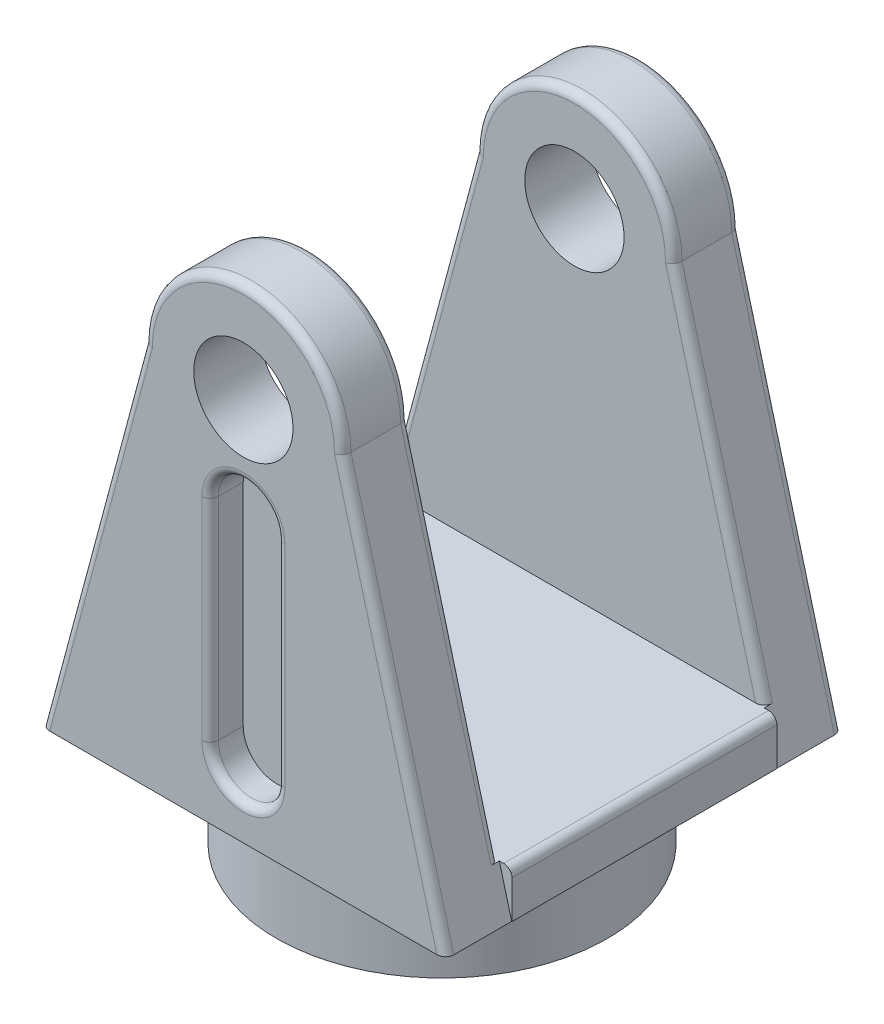
SolidWorks part; units mm, degrees
material "AISI 316 Stainless Steel Sheet (SS)"
ref_plane "Front Plane" through (0, 0, 0) normal (0, 0, 1) x (1, 0, 0)
ref_plane "Top Plane" through (0, 0, 0) normal (0, 1, 0) x (1, 0, 0)
ref_plane "Right Plane" through (0, 0, 0) normal (1, 0, 0) x (0, 0, -1)
sketch "Sketch2" plane through (0, 0, 0) normal (0, 0, 1) x (1, 0, 0)
  line L0 (-76.2, 0) -> (-155.088, -294.4142)
  line L1 (-76.2, 0) -> (-76.2, -251.8153) construction
  line L2 (76.2, 0) -> (155.088, -294.4142)
  line L3 (76.2, 0) -> (76.2, -294.4142) construction
  line L4 (-155.088, -294.4142) -> (155.088, -294.4142)
  circle A1 centre (0, 0) radius 38.1
  arc A2 (-76.2, 0) -> (76.2, 0) centre (0, 0) cw
  dimension "D1" = 310.1761
  dimension "D2" = 76.2
  dimension "D3" = 304.8
  dimension "D4" = 15
  dimension "D5" = 304.8
extrude "Boss-Extrude2" add sketch "Sketch2" along normal blind 50.8
sketch "Sketch4" plane through (0, 0, 50.8) normal (0, 0, 1) x (1, 0, 0)
  line L1 (-155.088, -294.4142) -> (155.3271, -294.4142)
  line L2 (-155.088, -294.4142) -> (-155.088, -258.9428)
  line L3 (-155.088, -258.9428) -> (155.3271, -258.9428)
  line L4 (155.3271, -294.4142) -> (155.3271, -258.9428)
extrude "Boss-Extrude4" add sketch "Sketch4" along normal blind 101.6 contours L3 L4 L1 L2
sketch "Sketch5" plane through (0, 0, 0) normal (0, 0, -1) x (-1, 0, 0)
  line L0 (0, -80.0813) -> (0, -242.2072) construction
  line L1 (25.5068, -80.0813) -> (25.5068, -242.2072)
  line L2 (-25.5068, -80.0813) -> (-25.5068, -242.2072)
  arc A0 (25.5068, -80.0813) -> (-25.5068, -80.0813) centre (0, -80.0813) ccw
  arc A1 (-25.5068, -242.2072) -> (25.5068, -242.2072) centre (0, -242.2072) ccw
  point P3 (0, -161.1443)
extrude "Cut-Extrude1" cut sketch "Sketch5" against normal blind 25.4
mirror "Mirror5" about plane through (0, 0, 152.4) normal (0, 0, -1) of bodies 109
fillet "Fillet1" radius 6.35 1 edges at (115.644, -147.2071, 304.8)
fillet "Fillet2" radius 6.35 1 edges at (-115.644, -147.2071, 304.8)
fillet "Fillet3" radius 6.35 1 edges at (0, 76.2, 304.8)
fillet "Fillet4" radius 6.35 4 edges at (0, -267.7141, 304.8) (25.5068, -161.1443, 304.8) (0, -54.5745, 304.8) (-25.5068, -161.1443, 304.8)
fillet "Fillet5" radius 6.35 15 edges at (110.8918, -129.4714, 50.8) (110.8918, -129.4714, 254) (0, -54.5745, 0) (0, -267.7141, 0) (-25.5068, -161.1443, 0) (25.5068, -161.1443, 0) (115.644, -147.2071, 0) (0, 76.2, 254) (-110.8918, -129.4714, 254) (0, 76.2, 50.8) (0, 76.2, 0) (-115.644, -147.2071, 0) (-110.8918, -129.4714, 50.8) (-155.088, -258.9428, 152.4) (155.3271, -258.9428, 152.4)
sketch "Sketch8" plane through (0, -294.4142, 0) normal (0, -1, 0) x (-1, 0, 0)
  line L0 (0, 0) -> (0, -304.8) construction
  line L1 (148.514, -304.8) -> (-148.514, -304.8) construction
  line L2 (155.088, -152.4) -> (-155.3271, -152.4) construction
  line L3 (155.088, -254) -> (155.088, -50.8) construction
  line L4 (-155.3271, -254) -> (-155.3271, -50.8) construction
  circle A0 centre (0, -152.4) radius 127
  dimension "D1" = 254
extrude "Boss-Extrude5" add sketch "Sketch8" along normal blind 76.2
